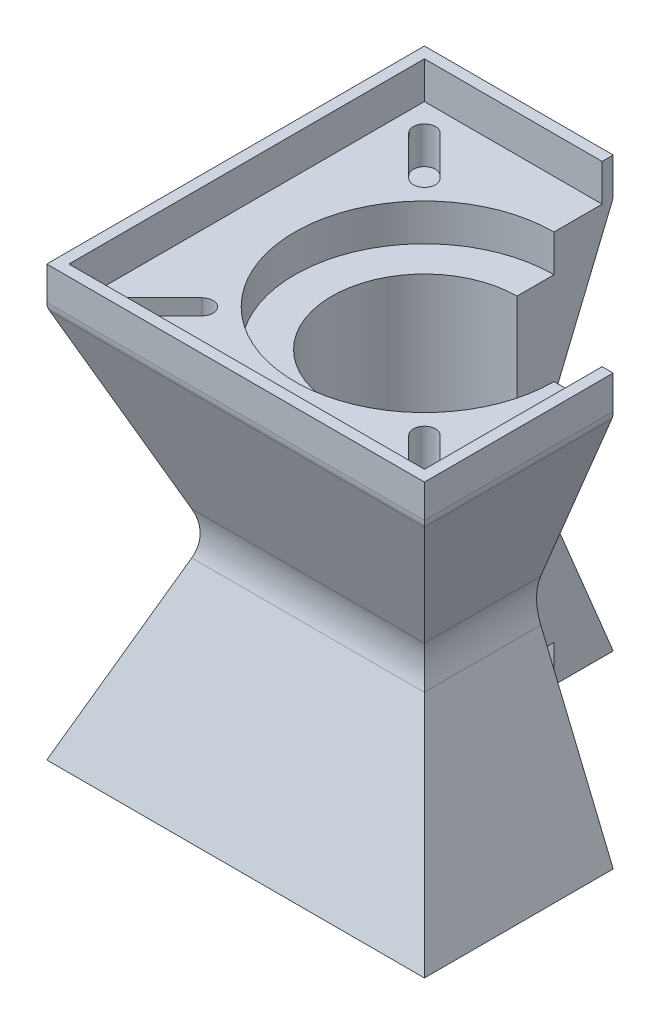
SolidWorks part; units mm, degrees
material "Cast Stainless Steel"
ref_plane "Front Plane" through (0, 0, 0) normal (0, 0, 1) x (1, 0, 0)
ref_plane "Top Plane" through (0, 0, 0) normal (0, 1, 0) x (1, 0, 0)
ref_plane "Right Plane" through (0, 0, 0) normal (1, 0, 0) x (0, 0, -1)
sketch "Sketch1" plane through (0, 0, 0) normal (0, 1, 0) x (1, 0, 0)
  line L1 (-51, -51) -> (51, -51)
  line L2 (-51, -51) -> (-51, 51)
  line L3 (-51, 51) -> (51, 51)
  line L4 (51, -51) -> (51, 51)
  line L5 (-51, -51) -> (51, 51) construction
  line L6 (-51, 51) -> (51, -51) construction
  point P0 (0, 0)
  dimension "D1" = 102
ref_plane "Plane1" through (0, 53, 0) normal (0, 1, 0) x (1, 0, 0)
sketch "Sketch2" plane through (0, 53, 0) normal (0, 1, 0) x (1, 0, 0)
  line L0 (-51, -51) -> (51, 51) construction
  line L1 (-29.0467, -29.0467) -> (29.0467, -29.0467)
  line L2 (-29.0467, -29.0467) -> (-29.0467, 29.0467)
  line L3 (-29.0467, 29.0467) -> (29.0467, 29.0467)
  line L4 (29.0467, -29.0467) -> (29.0467, 29.0467)
  line L5 (-29.0467, -29.0467) -> (29.0467, 29.0467) construction
  line L6 (-29.0467, 29.0467) -> (29.0467, -29.0467) construction
  point P0 (0, 0)
  dimension "D1" = 58.0934
loft "Loft1" add profiles "Sketch2", "Sketch1"
mirror "Mirror1" about plane through (0, 53, 0) normal (0, 1, 0) of "Loft1"
sketch "Sketch3" plane through (0, 106, 0) normal (0, 1, 0) x (1, 0, 0)
  circle A0 centre (0, 0) radius 25
  dimension "D1" = 50
extrude "Cut-Extrude1" cut sketch "Sketch3" against normal through all
sketch "Sketch4" plane through (0, 106, 0) normal (0, 1, 0) x (1, 0, 0)
  circle A0 centre (0, 0) radius 35
  dimension "D1" = 70
extrude "Cut-Extrude2" cut sketch "Sketch4" against normal blind 10
mirror "Mirror2" about plane through (0, 53, 0) normal (0, 1, 0) of "Cut-Extrude2"
fillet "Fillet1" radius 15 4 edges
sketch "Sketch5" plane through (0, 106, 0) normal (0, 1, 0) x (1, 0, 0)
  line L1 (0, 0) -> (51, 0)
  line L2 (0, 0) -> (0, 51)
  line L3 (0, 51) -> (51, 51)
  line L4 (51, 0) -> (51, 51)
extrude "Cut-Extrude3" cut sketch "Sketch5" against normal through all
sketch "Sketch6" plane through (0, 106, 0) normal (0, 1, 0) x (1, 0, 0)
  line L0 (0, 51) -> (-51, 51) construction
  line L1 (-51, 51) -> (-51, -51) construction
  line L2 (51, -51) -> (51, 0) construction
  line L3 (-51, -51) -> (51, -51) construction
  line L4 (0, 51) -> (-51, 51)
  line L5 (-51, 51) -> (-51, -51)
  line L6 (51, -51) -> (51, 0)
  line L7 (-51, -51) -> (51, -51)
  line L8 (0, 48) -> (-48, 48)
  line L9 (-48, 48) -> (-48, -48)
  line L10 (-48, -48) -> (48, -48)
  line L11 (48, -48) -> (48, 0)
  line L12 (51, 0) -> (48, 0)
  line L13 (0, 48) -> (0, 51)
  dimension "D1" = 3
extrude "Boss-Extrude1" add sketch "Sketch6" along normal blind 10
sketch "Sketch7" plane through (0, 106, 0) normal (0, 1, 0) x (1, 0, 0)
  line L0 (0, 0) -> (-48, 48) construction
  line L1 (-30.052, 30.052) -> (-40.6586, 40.6586) construction
  line L2 (-32.1734, 27.9307) -> (-42.78, 38.5373)
  line L3 (-27.9307, 32.1734) -> (-38.5373, 42.78)
  line L4 (30.052, 30.052) -> (40.6586, 40.6586) construction
  line L5 (27.9307, 32.1734) -> (38.5373, 42.78)
  line L6 (32.1734, 27.9307) -> (42.78, 38.5373)
  line L7 (30.052, -30.052) -> (40.6586, -40.6586) construction
  line L8 (32.1734, -27.9307) -> (42.78, -38.5373)
  line L9 (27.9307, -32.1734) -> (38.5373, -42.78)
  line L10 (-30.052, -30.052) -> (-40.6586, -40.6586) construction
  line L11 (-27.9307, -32.1734) -> (-38.5373, -42.78)
  line L12 (-32.1734, -27.9307) -> (-42.78, -38.5373)
  circle A0 centre (0, 0) radius 50 construction
  arc A1 (-32.1734, 27.9307) -> (-27.9307, 32.1734) centre (-30.052, 30.052) ccw
  arc A2 (-38.5373, 42.78) -> (-42.78, 38.5373) centre (-40.6586, 40.6586) ccw
  arc A3 (27.9307, 32.1734) -> (32.1734, 27.9307) centre (30.052, 30.052) ccw
  arc A4 (42.78, 38.5373) -> (38.5373, 42.78) centre (40.6586, 40.6586) ccw
  arc A5 (32.1734, -27.9307) -> (27.9307, -32.1734) centre (30.052, -30.052) ccw
  arc A6 (38.5373, -42.78) -> (42.78, -38.5373) centre (40.6586, -40.6586) ccw
  arc A7 (-27.9307, -32.1734) -> (-32.1734, -27.9307) centre (-30.052, -30.052) ccw
  arc A8 (-42.78, -38.5373) -> (-38.5373, -42.78) centre (-40.6586, -40.6586) ccw
  point P7 (-35.3553, 35.3553)
  point P12 (0, 0)
  point P13 (32.1734, -27.9307)
  point P17 (35.3553, 35.3553)
  point P24 (35.3553, -35.3553)
  point P31 (-35.3553, -35.3553)
  point P36 (0, 0)
  dimension "D1" = 100
  dimension "D3" = 3
  dimension "D2" = 15
  dimension "D4" = 4
extrude "Cut-Extrude4" cut sketch "Sketch7" against normal blind 10
fillet "Fillet2" radius 5 4 edges
